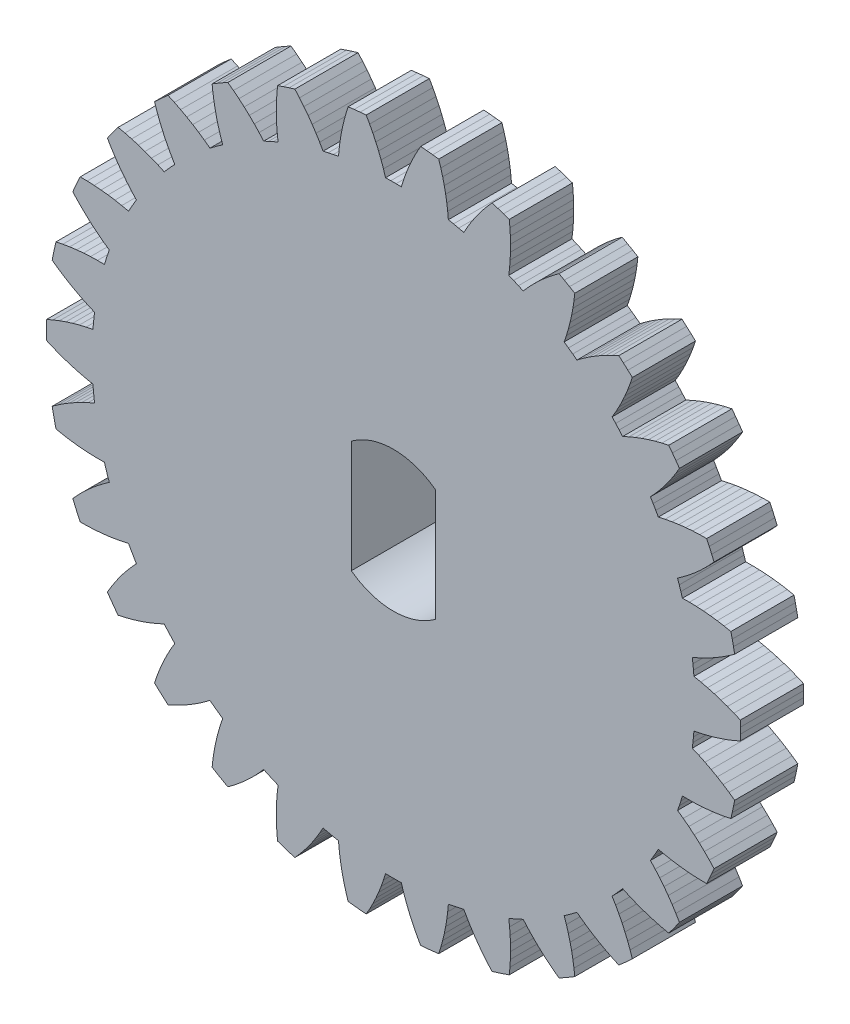
SolidWorks part; units mm, degrees
ref_plane "Front Plane" through (0, 0, 0) normal (0, 0, 1) x (1, 0, 0)
ref_plane "Top Plane" through (0, 0, 0) normal (0, 1, 0) x (1, 0, 0)
ref_plane "Right Plane" through (0, 0, 0) normal (1, 0, 0) x (0, 0, -1)
sketch "Sketch2" plane through (0, 0, 0) normal (0, 0, 1) x (1, 0, 0)
  line L20 (0.2811, 27.0228) -> (0.3553, 27.2598)
  line L21 (0.3553, 27.2598) -> (0.4378, 27.494)
  line L22 (0.4378, 27.494) -> (0.5284, 27.7252)
  line L23 (0.5284, 27.7252) -> (0.6271, 27.953)
  line L24 (0.6271, 27.953) -> (0.7337, 28.1773)
  line L25 (0.7337, 28.1773) -> (0.8481, 28.3976)
  line L26 (0.8481, 28.3976) -> (0.9702, 28.6139)
  line L27 (1.1852, 28.5951) -> (0.9702, 28.6139)
  line L28 (1.3998, 28.5725) -> (1.1852, 28.5951)
  line L29 (1.614, 28.5462) -> (1.3998, 28.5725)
  line L30 (1.614, 28.5462) -> (1.6885, 28.3093)
  line L31 (1.6885, 28.3093) -> (1.7546, 28.07)
  line L32 (1.7546, 28.07) -> (1.8122, 27.8285)
  line L33 (1.8122, 27.8285) -> (1.8614, 27.5851)
  line L34 (1.8614, 27.5851) -> (1.9019, 27.3401)
  line L35 (1.9019, 27.3401) -> (1.9339, 27.0939)
  line L36 (1.9339, 27.0939) -> (1.9572, 26.8467)
  line L37 (1.9572, 26.8467) -> (2.1412, 26.8109)
  line L38 (2.1412, 26.8109) -> (2.3246, 26.7719)
  line L39 (2.3246, 26.7719) -> (2.5072, 26.7298)
  line L41 (2.5072, 26.7298) -> (2.6291, 26.9461)
  line L42 (2.6291, 26.9461) -> (2.7584, 27.1581)
  line L43 (2.7584, 27.1581) -> (2.8951, 27.3653)
  line L44 (2.8951, 27.3653) -> (3.039, 27.5677)
  line L45 (3.039, 27.5677) -> (3.1899, 27.7649)
  line L46 (3.1899, 27.7649) -> (3.3476, 27.9567)
  line L47 (3.3476, 27.9567) -> (3.512, 28.1428)
  line L48 (3.7184, 28.0797) -> (3.512, 28.1428)
  line L49 (3.9236, 28.013) -> (3.7184, 28.0797)
  line L50 (4.1277, 27.9427) -> (3.9236, 28.013)
  line L51 (4.1277, 27.9427) -> (4.1513, 27.6955)
  line L52 (4.1513, 27.6955) -> (4.1661, 27.4477)
  line L53 (4.1661, 27.4477) -> (4.1723, 27.1995)
  line L54 (4.1723, 27.1995) -> (4.1698, 26.9512)
  line L55 (4.1698, 26.9512) -> (4.1586, 26.7031)
  line L56 (4.1586, 26.7031) -> (4.1386, 26.4556)
  line L57 (4.1386, 26.4556) -> (4.11, 26.209)
  line L58 (4.11, 26.209) -> (4.2826, 26.1357)
  line L59 (4.2826, 26.1357) -> (4.4538, 26.0595)
  line L60 (4.4538, 26.0595) -> (4.6237, 25.9803)
  line L61 (4.6237, 25.9803) -> (4.7879, 26.1666)
  line L62 (4.7879, 26.1666) -> (4.9585, 26.347)
  line L63 (4.9585, 26.347) -> (5.1353, 26.5213)
  line L64 (5.1353, 26.5213) -> (5.3181, 26.6893)
  line L65 (5.3181, 26.6893) -> (5.5067, 26.8508)
  line L66 (5.5067, 26.8508) -> (5.7008, 27.0056)
  line L67 (5.7008, 27.0056) -> (5.9003, 27.1535)
  line L68 (6.0891, 27.0489) -> (5.9003, 27.1535)
  line L69 (6.276, 26.941) -> (6.0891, 27.0489)
  line L70 (6.461, 26.8298) -> (6.276, 26.941)
  line L71 (6.461, 26.8298) -> (6.4326, 26.5831)
  line L72 (6.4326, 26.5831) -> (6.3956, 26.3376)
  line L73 (6.3956, 26.3376) -> (6.3501, 26.0935)
  line L74 (6.3501, 26.0935) -> (6.296, 25.8512)
  line L75 (6.296, 25.8512) -> (6.2334, 25.6109)
  line L76 (6.2334, 25.6109) -> (6.1625, 25.3729)
  line L77 (6.1625, 25.3729) -> (6.0832, 25.1376)
  line L78 (6.0832, 25.1376) -> (6.2368, 25.0301)
  line L79 (6.2368, 25.0301) -> (6.3884, 24.9199)
  line L80 (6.3884, 24.9199) -> (6.5381, 24.8071)
  line L81 (6.5381, 24.8071) -> (6.7374, 24.9552)
  line L82 (6.7374, 24.9552) -> (6.9418, 25.0962)
  line L83 (6.9418, 25.0962) -> (7.151, 25.23)
  line L84 (7.151, 25.23) -> (7.3648, 25.3563)
  line L85 (7.3648, 25.3563) -> (7.5828, 25.4751)
  line L86 (7.5828, 25.4751) -> (7.8049, 25.5861)
  line L87 (7.8049, 25.5861) -> (8.0307, 25.6893)
  line L88 (8.1936, 25.5477) -> (8.0307, 25.6893)
  line L89 (8.354, 25.4033) -> (8.1936, 25.5477)
  line L90 (8.5118, 25.2561) -> (8.354, 25.4033)
  line L91 (8.5118, 25.2561) -> (8.4328, 25.0207)
  line L92 (8.4328, 25.0207) -> (8.3456, 24.7882)
  line L93 (8.3456, 24.7882) -> (8.2503, 24.559)
  line L94 (8.2503, 24.559) -> (8.147, 24.3332)
  line L95 (8.147, 24.3332) -> (8.0359, 24.1111)
  line L96 (8.0359, 24.1111) -> (7.917, 23.8931)
  line L97 (7.917, 23.8931) -> (7.7905, 23.6794)
  line L98 (7.7905, 23.6794) -> (7.9184, 23.5424)
  line L99 (7.9184, 23.5424) -> (8.0438, 23.4031)
  line L100 (8.0438, 23.4031) -> (8.1668, 23.2616)
  line L101 (8.1668, 23.2616) -> (8.3925, 23.365)
  line L102 (8.3925, 23.365) -> (8.6217, 23.4604)
  line L103 (8.6217, 23.4604) -> (8.8542, 23.5478)
  line L104 (8.8542, 23.5478) -> (9.0895, 23.6269)
  line L105 (9.0895, 23.6269) -> (9.3275, 23.6977)
  line L106 (9.3275, 23.6977) -> (9.5678, 23.7602)
  line L107 (9.5678, 23.7602) -> (9.8102, 23.8141)
  line L108 (9.9401, 23.6418) -> (9.8102, 23.8141)
  line L109 (10.0669, 23.4672) -> (9.9401, 23.6418)
  line L110 (10.1907, 23.2904) -> (10.0669, 23.4672)
  line L111 (10.1907, 23.2904) -> (10.0645, 23.0766)
  line L112 (10.0645, 23.0766) -> (9.9309, 22.8673)
  line L113 (9.9309, 22.8673) -> (9.79, 22.6629)
  line L114 (9.79, 22.6629) -> (9.642, 22.4635)
  line L115 (9.642, 22.4635) -> (9.4871, 22.2694)
  line L116 (9.4871, 22.2694) -> (9.3255, 22.0809)
  line L117 (9.3255, 22.0809) -> (9.1574, 21.8981)
  line L118 (9.1574, 21.8981) -> (9.2539, 21.7375)
  line L119 (9.2539, 21.7375) -> (9.3476, 21.5751)
  line L120 (9.3476, 21.5751) -> (9.4385, 21.4112)
  line L121 (9.4385, 21.4112) -> (9.6808, 21.4654)
  line L122 (9.6808, 21.4654) -> (9.9249, 21.5111)
  line L123 (9.9249, 21.5111) -> (10.1704, 21.5482)
  line L124 (10.1704, 21.5482) -> (10.4171, 21.5767)
  line L125 (10.4171, 21.5767) -> (10.6646, 21.5965)
  line L126 (10.6646, 21.5965) -> (10.9126, 21.6076)
  line L127 (10.9126, 21.6076) -> (11.1609, 21.61)
  line L128 (11.2521, 21.4144) -> (11.1609, 21.61)
  line L129 (11.3399, 21.2172) -> (11.2521, 21.4144)
  line L130 (11.4242, 21.0186) -> (11.3399, 21.2172)
  line L131 (11.4242, 21.0186) -> (11.2563, 20.8357)
  line L132 (11.2563, 20.8357) -> (11.0821, 20.6588)
  line L133 (11.0821, 20.6588) -> (10.9017, 20.4881)
  line L134 (10.9017, 20.4881) -> (10.7155, 20.3238)
  line L135 (10.7155, 20.3238) -> (10.5237, 20.1662)
  line L136 (10.5237, 20.1662) -> (10.3264, 20.0154)
  line L137 (10.3264, 20.0154) -> (10.124, 19.8716)
  line L138 (10.124, 19.8716) -> (10.185, 19.6944)
  line L139 (10.185, 19.6944) -> (10.2429, 19.5161)
  line L140 (10.2429, 19.5161) -> (10.2977, 19.3368)
  line L141 (10.2977, 19.3368) -> (10.546, 19.3395)
  line L142 (10.546, 19.3395) -> (10.7943, 19.3334)
  line L143 (10.7943, 19.3334) -> (11.0421, 19.3187)
  line L144 (11.0421, 19.3187) -> (11.2893, 19.2952)
  line L145 (11.2893, 19.2952) -> (11.5355, 19.2631)
  line L146 (11.5355, 19.2631) -> (11.7805, 19.2224)
  line L147 (11.7805, 19.2224) -> (12.0238, 19.1732)
  line L148 (12.0724, 18.9629) -> (12.0238, 19.1732)
  line L149 (12.1172, 18.7518) -> (12.0724, 18.9629)
  line L150 (12.1584, 18.5399) -> (12.1172, 18.7518)
  line L151 (12.1584, 18.5399) -> (11.9561, 18.3959)
  line L152 (11.9561, 18.3959) -> (11.7489, 18.2591)
  line L153 (11.7489, 18.2591) -> (11.5371, 18.1297)
  line L154 (11.5371, 18.1297) -> (11.3208, 18.0077)
  line L155 (11.3208, 18.0077) -> (11.1003, 17.8934)
  line L156 (11.1003, 17.8934) -> (10.876, 17.7869)
  line L157 (10.876, 17.7869) -> (10.6481, 17.6884)
  line L158 (10.6481, 17.6884) -> (10.671, 17.5023)
  line L159 (10.671, 17.5023) -> (10.6906, 17.3159)
  line L160 (10.6906, 17.3159) -> (10.7069, 17.1291)
  line L161 (10.7069, 17.1291) -> (10.9503, 17.0801)
  line L162 (10.9503, 17.0801) -> (11.1919, 17.0226)
  line L163 (11.1919, 17.0226) -> (11.4312, 16.9566)
  line L164 (11.4312, 16.9566) -> (11.6682, 16.8823)
  line L165 (11.6682, 16.8823) -> (11.9023, 16.7997)
  line L166 (11.9023, 16.7997) -> (12.1335, 16.709)
  line L167 (12.1335, 16.709) -> (12.3613, 16.6102)
  line L168 (12.365, 16.3944) -> (12.3613, 16.6102)
  line L169 (12.365, 16.1786) -> (12.365, 16.3944)
  line L170 (12.3613, 15.9628) -> (12.365, 16.1786)
  line L171 (12.3613, 15.9628) -> (12.1335, 15.864)
  line L172 (12.1335, 15.864) -> (11.9023, 15.7733)
  line L173 (11.9023, 15.7733) -> (11.6682, 15.6907)
  line L174 (11.6682, 15.6907) -> (11.4312, 15.6164)
  line L175 (11.4312, 15.6164) -> (11.1919, 15.5504)
  line L176 (11.1919, 15.5504) -> (10.9503, 15.4929)
  line L177 (10.9503, 15.4929) -> (10.7069, 15.4438)
  line L178 (10.7069, 15.4438) -> (10.6906, 15.2571)
  line L179 (10.6906, 15.2571) -> (10.671, 15.0707)
  line L180 (10.671, 15.0707) -> (10.6481, 14.8846)
  line L181 (10.6481, 14.8846) -> (10.876, 14.7861)
  line L182 (10.876, 14.7861) -> (11.1003, 14.6796)
  line L183 (11.1003, 14.6796) -> (11.3208, 14.5653)
  line L184 (11.3208, 14.5653) -> (11.5371, 14.4433)
  line L185 (11.5371, 14.4433) -> (11.7489, 14.3139)
  line L186 (11.7489, 14.3139) -> (11.9561, 14.1771)
  line L187 (11.9561, 14.1771) -> (12.1584, 14.0331)
  line L188 (12.1172, 13.8212) -> (12.1584, 14.0331)
  line L189 (12.0724, 13.6101) -> (12.1172, 13.8212)
  line L190 (12.0238, 13.3998) -> (12.0724, 13.6101)
  line L191 (12.0238, 13.3998) -> (11.7805, 13.3506)
  line L192 (11.7805, 13.3506) -> (11.5355, 13.3098)
  line L193 (11.5355, 13.3098) -> (11.2893, 13.2778)
  line L194 (11.2893, 13.2778) -> (11.0421, 13.2543)
  line L195 (11.0421, 13.2543) -> (10.7943, 13.2396)
  line L196 (10.7943, 13.2396) -> (10.546, 13.2335)
  line L197 (10.546, 13.2335) -> (10.2977, 13.2362)
  line L198 (10.2977, 13.2362) -> (10.2429, 13.0569)
  line L199 (10.2429, 13.0569) -> (10.185, 12.8786)
  line L200 (10.185, 12.8786) -> (10.124, 12.7014)
  line L201 (10.124, 12.7014) -> (10.3264, 12.5576)
  line L202 (10.3264, 12.5576) -> (10.5237, 12.4068)
  line L203 (10.5237, 12.4068) -> (10.7155, 12.2492)
  line L204 (10.7155, 12.2492) -> (10.9017, 12.0849)
  line L205 (10.9017, 12.0849) -> (11.0821, 11.9142)
  line L206 (11.0821, 11.9142) -> (11.2563, 11.7373)
  line L207 (11.2563, 11.7373) -> (11.4242, 11.5544)
  line L208 (11.3399, 11.3558) -> (11.4242, 11.5544)
  line L209 (11.2521, 11.1586) -> (11.3399, 11.3558)
  line L210 (11.1609, 10.963) -> (11.2521, 11.1586)
  line L211 (11.1609, 10.963) -> (10.9126, 10.9654)
  line L212 (10.9126, 10.9654) -> (10.6646, 10.9765)
  line L213 (10.6646, 10.9765) -> (10.4171, 10.9963)
  line L214 (10.4171, 10.9963) -> (10.1704, 11.0248)
  line L215 (10.1704, 11.0248) -> (9.9249, 11.0619)
  line L216 (9.9249, 11.0619) -> (9.6808, 11.1076)
  line L217 (9.6808, 11.1076) -> (9.4385, 11.1618)
  line L218 (9.4385, 11.1618) -> (9.3476, 10.9979)
  line L219 (9.3476, 10.9979) -> (9.2539, 10.8355)
  line L220 (9.2539, 10.8355) -> (9.1574, 10.6748)
  line L221 (9.1574, 10.6748) -> (9.3255, 10.4921)
  line L222 (9.3255, 10.4921) -> (9.4871, 10.3036)
  line L223 (9.4871, 10.3036) -> (9.642, 10.1095)
  line L224 (9.642, 10.1095) -> (9.79, 9.9101)
  line L225 (9.79, 9.9101) -> (9.9309, 9.7057)
  line L226 (9.9309, 9.7057) -> (10.0645, 9.4964)
  line L227 (10.0645, 9.4964) -> (10.1907, 9.2826)
  line L228 (10.0669, 9.1058) -> (10.1907, 9.2826)
  line L229 (9.9401, 8.9312) -> (10.0669, 9.1058)
  line L230 (9.8102, 8.7589) -> (9.9401, 8.9312)
  line L231 (9.8102, 8.7589) -> (9.5678, 8.8128)
  line L232 (9.5678, 8.8128) -> (9.3275, 8.8753)
  line L233 (9.3275, 8.8753) -> (9.0895, 8.9461)
  line L234 (9.0895, 8.9461) -> (8.8542, 9.0252)
  line L235 (8.8542, 9.0252) -> (8.6217, 9.1126)
  line L236 (8.6217, 9.1126) -> (8.3925, 9.208)
  line L237 (8.3925, 9.208) -> (8.1668, 9.3114)
  line L238 (8.1668, 9.3114) -> (8.0438, 9.1699)
  line L239 (8.0438, 9.1699) -> (7.9184, 9.0306)
  line L240 (7.9184, 9.0306) -> (7.7905, 8.8936)
  line L241 (7.7905, 8.8936) -> (7.917, 8.6799)
  line L242 (7.917, 8.6799) -> (8.0359, 8.4619)
  line L243 (8.0359, 8.4619) -> (8.147, 8.2398)
  line L244 (8.147, 8.2398) -> (8.2503, 8.014)
  line L245 (8.2503, 8.014) -> (8.3456, 7.7848)
  line L246 (8.3456, 7.7848) -> (8.4328, 7.5523)
  line L247 (8.4328, 7.5523) -> (8.5118, 7.3169)
  line L248 (8.354, 7.1697) -> (8.5118, 7.3169)
  line L249 (8.1936, 7.0253) -> (8.354, 7.1697)
  line L250 (8.0307, 6.8837) -> (8.1936, 7.0253)
  line L251 (8.0307, 6.8837) -> (7.8049, 6.9869)
  line L252 (7.8049, 6.9869) -> (7.5828, 7.0979)
  line L253 (7.5828, 7.0979) -> (7.3647, 7.2167)
  line L254 (7.3647, 7.2167) -> (7.151, 7.343)
  line L255 (7.151, 7.343) -> (6.9418, 7.4768)
  line L256 (6.9418, 7.4768) -> (6.7374, 7.6178)
  line L257 (6.7374, 7.6178) -> (6.5381, 7.7659)
  line L258 (6.5381, 7.7659) -> (6.3884, 7.6531)
  line L259 (6.3884, 7.6531) -> (6.2368, 7.5429)
  line L260 (6.2368, 7.5429) -> (6.0832, 7.4354)
  line L261 (6.0832, 7.4354) -> (6.1625, 7.2)
  line L262 (6.1625, 7.2) -> (6.2334, 6.9621)
  line L263 (6.2334, 6.9621) -> (6.296, 6.7218)
  line L264 (6.296, 6.7218) -> (6.3501, 6.4795)
  line L265 (6.3501, 6.4795) -> (6.3956, 6.2354)
  line L266 (6.3956, 6.2354) -> (6.4326, 5.9899)
  line L267 (6.4326, 5.9899) -> (6.4609, 5.7432)
  line L268 (6.276, 5.632) -> (6.4609, 5.7432)
  line L269 (6.0891, 5.5241) -> (6.276, 5.632)
  line L270 (5.9003, 5.4195) -> (6.0891, 5.5241)
  line L271 (5.9003, 5.4195) -> (5.7008, 5.5674)
  line L272 (5.7008, 5.5674) -> (5.5067, 5.7222)
  line L273 (5.5067, 5.7222) -> (5.3181, 5.8837)
  line L274 (5.3181, 5.8837) -> (5.1353, 6.0517)
  line L275 (5.1353, 6.0517) -> (4.9585, 6.226)
  line L276 (4.9585, 6.226) -> (4.7879, 6.4064)
  line L277 (4.7879, 6.4064) -> (4.6237, 6.5927)
  line L278 (4.6237, 6.5927) -> (4.4538, 6.5135)
  line L279 (4.4538, 6.5135) -> (4.2826, 6.4372)
  line L280 (4.2826, 6.4372) -> (4.11, 6.364)
  line L281 (4.11, 6.364) -> (4.1386, 6.1174)
  line L282 (4.1386, 6.1174) -> (4.1585, 5.8699)
  line L283 (4.1585, 5.8699) -> (4.1698, 5.6218)
  line L284 (4.1698, 5.6218) -> (4.1723, 5.3735)
  line L285 (4.1723, 5.3735) -> (4.1661, 5.1253)
  line L286 (4.1661, 5.1253) -> (4.1512, 4.8775)
  line L287 (4.1512, 4.8775) -> (4.1277, 4.6303)
  line L288 (3.9236, 4.56) -> (4.1277, 4.6303)
  line L289 (3.7184, 4.4933) -> (3.9236, 4.56)
  line L290 (3.512, 4.4302) -> (3.7184, 4.4933)
  line L291 (3.512, 4.4302) -> (3.3476, 4.6163)
  line L292 (3.3476, 4.6163) -> (3.1899, 4.8081)
  line L293 (3.1899, 4.8081) -> (3.039, 5.0053)
  line L294 (3.039, 5.0053) -> (2.8951, 5.2076)
  line L295 (2.8951, 5.2076) -> (2.7584, 5.4149)
  line L296 (2.7584, 5.4149) -> (2.629, 5.6269)
  line L297 (2.629, 5.6269) -> (2.5072, 5.8432)
  line L298 (2.5072, 5.8432) -> (2.3246, 5.8011)
  line L299 (2.3246, 5.8011) -> (2.1412, 5.7621)
  line L300 (2.1412, 5.7621) -> (1.9572, 5.7263)
  line L301 (1.9572, 5.7263) -> (1.9339, 5.4791)
  line L302 (1.9339, 5.4791) -> (1.9019, 5.2329)
  line L303 (1.9019, 5.2329) -> (1.8613, 4.9879)
  line L304 (1.8613, 4.9879) -> (1.8122, 4.7445)
  line L305 (1.8122, 4.7445) -> (1.7545, 4.503)
  line L306 (1.7545, 4.503) -> (1.6885, 4.2637)
  line L307 (1.6885, 4.2637) -> (1.614, 4.0268)
  line L308 (1.3998, 4.0005) -> (1.614, 4.0268)
  line L309 (1.1852, 3.9779) -> (1.3998, 4.0005)
  line L310 (0.9702, 3.9591) -> (1.1852, 3.9779)
  line L311 (0.9702, 3.9591) -> (0.8481, 4.1754)
  line L312 (0.8481, 4.1754) -> (0.7337, 4.3957)
  line L313 (0.7337, 4.3957) -> (0.6271, 4.62)
  line L314 (0.6271, 4.62) -> (0.5284, 4.8478)
  line L315 (0.5284, 4.8478) -> (0.4378, 5.079)
  line L316 (0.4378, 5.079) -> (0.3553, 5.3132)
  line L317 (0.3553, 5.3132) -> (0.2811, 5.5502)
  line L318 (0.2811, 5.5502) -> (0.0937, 5.5469)
  line L319 (0.0937, 5.5469) -> (-0.0937, 5.5469)
  line L320 (-0.0937, 5.5469) -> (-0.2811, 5.5502)
  line L321 (-0.2811, 5.5502) -> (-0.3553, 5.3132)
  line L322 (-0.3553, 5.3132) -> (-0.4378, 5.079)
  line L323 (-0.4378, 5.079) -> (-0.5284, 4.8478)
  line L324 (-0.5284, 4.8478) -> (-0.6271, 4.62)
  line L325 (-0.6271, 4.62) -> (-0.7337, 4.3957)
  line L326 (-0.7337, 4.3957) -> (-0.8481, 4.1754)
  line L327 (-0.8481, 4.1754) -> (-0.9702, 3.9591)
  line L328 (-1.1852, 3.9779) -> (-0.9702, 3.9591)
  line L329 (-1.3998, 4.0005) -> (-1.1852, 3.9779)
  line L330 (-1.614, 4.0268) -> (-1.3998, 4.0005)
  line L331 (-1.614, 4.0268) -> (-1.6885, 4.2637)
  line L332 (-1.6885, 4.2637) -> (-1.7546, 4.503)
  line L333 (-1.7546, 4.503) -> (-1.8122, 4.7445)
  line L334 (-1.8122, 4.7445) -> (-1.8614, 4.9879)
  line L335 (-1.8614, 4.9879) -> (-1.9019, 5.2329)
  line L336 (-1.9019, 5.2329) -> (-1.9339, 5.4791)
  line L337 (-1.9339, 5.4791) -> (-1.9572, 5.7263)
  line L338 (-1.9572, 5.7263) -> (-2.1412, 5.7621)
  line L339 (-2.1412, 5.7621) -> (-2.3246, 5.8011)
  line L340 (-2.3246, 5.8011) -> (-2.5072, 5.8432)
  line L341 (-2.5072, 5.8432) -> (-2.6291, 5.6269)
  line L342 (-2.6291, 5.6269) -> (-2.7584, 5.4149)
  line L343 (-2.7584, 5.4149) -> (-2.8951, 5.2077)
  line L344 (-2.8951, 5.2077) -> (-3.039, 5.0053)
  line L345 (-3.039, 5.0053) -> (-3.1899, 4.8081)
  line L346 (-3.1899, 4.8081) -> (-3.3476, 4.6163)
  line L347 (-3.3476, 4.6163) -> (-3.512, 4.4302)
  line L348 (-3.7184, 4.4933) -> (-3.512, 4.4302)
  line L349 (-3.9236, 4.56) -> (-3.7184, 4.4933)
  line L350 (-4.1277, 4.6303) -> (-3.9236, 4.56)
  line L351 (-4.1277, 4.6303) -> (-4.1513, 4.8775)
  line L352 (-4.1513, 4.8775) -> (-4.1661, 5.1253)
  line L353 (-4.1661, 5.1253) -> (-4.1723, 5.3735)
  line L354 (-4.1723, 5.3735) -> (-4.1698, 5.6218)
  line L355 (-4.1698, 5.6218) -> (-4.1586, 5.8699)
  line L356 (-4.1586, 5.8699) -> (-4.1386, 6.1174)
  line L357 (-4.1386, 6.1174) -> (-4.11, 6.364)
  line L358 (-4.11, 6.364) -> (-4.2826, 6.4372)
  line L359 (-4.2826, 6.4372) -> (-4.4538, 6.5135)
  line L360 (-4.4538, 6.5135) -> (-4.6237, 6.5927)
  line L361 (-4.6237, 6.5927) -> (-4.7879, 6.4064)
  line L362 (-4.7879, 6.4064) -> (-4.9585, 6.226)
  line L363 (-4.9585, 6.226) -> (-5.1353, 6.0517)
  line L364 (-5.1353, 6.0517) -> (-5.3181, 5.8837)
  line L365 (-5.3181, 5.8837) -> (-5.5067, 5.7222)
  line L366 (-5.5067, 5.7222) -> (-5.7008, 5.5674)
  line L367 (-5.7008, 5.5674) -> (-5.9003, 5.4195)
  line L368 (-6.0891, 5.5241) -> (-5.9003, 5.4195)
  line L369 (-6.276, 5.632) -> (-6.0891, 5.5241)
  line L370 (-6.461, 5.7432) -> (-6.276, 5.632)
  line L371 (-6.461, 5.7432) -> (-6.4326, 5.9899)
  line L372 (-6.4326, 5.9899) -> (-6.3956, 6.2354)
  line L373 (-6.3956, 6.2354) -> (-6.3501, 6.4795)
  line L374 (-6.3501, 6.4795) -> (-6.296, 6.7218)
  line L375 (-6.296, 6.7218) -> (-6.2334, 6.9621)
  line L376 (-6.2334, 6.9621) -> (-6.1625, 7.2)
  line L377 (-6.1625, 7.2) -> (-6.0832, 7.4354)
  line L378 (-6.0832, 7.4354) -> (-6.2368, 7.5429)
  line L379 (-6.2368, 7.5429) -> (-6.3884, 7.6531)
  line L380 (-6.3884, 7.6531) -> (-6.5381, 7.7659)
  line L381 (-6.5381, 7.7659) -> (-6.7374, 7.6178)
  line L382 (-6.7374, 7.6178) -> (-6.9418, 7.4768)
  line L383 (-6.9418, 7.4768) -> (-7.151, 7.343)
  line L384 (-7.151, 7.343) -> (-7.3648, 7.2167)
  line L385 (-7.3648, 7.2167) -> (-7.5828, 7.0979)
  line L386 (-7.5828, 7.0979) -> (-7.8049, 6.9869)
  line L387 (-7.8049, 6.9869) -> (-8.0307, 6.8837)
  line L388 (-8.1936, 7.0253) -> (-8.0307, 6.8837)
  line L389 (-8.354, 7.1697) -> (-8.1936, 7.0253)
  line L390 (-8.5118, 7.3169) -> (-8.354, 7.1697)
  line L391 (-8.5118, 7.3169) -> (-8.4328, 7.5523)
  line L392 (-8.4328, 7.5523) -> (-8.3456, 7.7848)
  line L393 (-8.3456, 7.7848) -> (-8.2503, 8.014)
  line L394 (-8.2503, 8.014) -> (-8.147, 8.2398)
  line L395 (-8.147, 8.2398) -> (-8.0359, 8.4619)
  line L396 (-8.0359, 8.4619) -> (-7.917, 8.6799)
  line L397 (-7.917, 8.6799) -> (-7.7905, 8.8936)
  line L398 (-7.7905, 8.8936) -> (-7.9184, 9.0306)
  line L399 (-7.9184, 9.0306) -> (-8.0438, 9.1699)
  line L400 (-8.0438, 9.1699) -> (-8.1668, 9.3114)
  line L401 (-8.1668, 9.3114) -> (-8.3925, 9.208)
  line L402 (-8.3925, 9.208) -> (-8.6218, 9.1126)
  line L403 (-8.6218, 9.1126) -> (-8.8542, 9.0252)
  line L404 (-8.8542, 9.0252) -> (-9.0895, 8.9461)
  line L405 (-9.0895, 8.9461) -> (-9.3275, 8.8753)
  line L406 (-9.3275, 8.8753) -> (-9.5678, 8.8128)
  line L407 (-9.5678, 8.8128) -> (-9.8102, 8.7589)
  line L408 (-9.9401, 8.9312) -> (-9.8102, 8.7589)
  line L409 (-10.0669, 9.1058) -> (-9.9401, 8.9312)
  line L410 (-10.1907, 9.2826) -> (-10.0669, 9.1058)
  line L411 (-10.1907, 9.2826) -> (-10.0645, 9.4964)
  line L412 (-10.0645, 9.4964) -> (-9.9309, 9.7057)
  line L413 (-9.9309, 9.7057) -> (-9.79, 9.9101)
  line L414 (-9.79, 9.9101) -> (-9.642, 10.1095)
  line L415 (-9.642, 10.1095) -> (-9.4871, 10.3036)
  line L416 (-9.4871, 10.3036) -> (-9.3255, 10.4921)
  line L417 (-9.3255, 10.4921) -> (-9.1574, 10.6749)
  line L418 (-9.1574, 10.6749) -> (-9.2539, 10.8355)
  line L419 (-9.2539, 10.8355) -> (-9.3476, 10.9979)
  line L420 (-9.3476, 10.9979) -> (-9.4385, 11.1618)
  line L421 (-9.4385, 11.1618) -> (-9.6808, 11.1076)
  line L422 (-9.6808, 11.1076) -> (-9.9249, 11.0619)
  line L423 (-9.9249, 11.0619) -> (-10.1704, 11.0248)
  line L424 (-10.1704, 11.0248) -> (-10.4171, 10.9963)
  line L425 (-10.4171, 10.9963) -> (-10.6646, 10.9765)
  line L426 (-10.6646, 10.9765) -> (-10.9126, 10.9654)
  line L427 (-10.9126, 10.9654) -> (-11.1609, 10.963)
  line L428 (-11.2521, 11.1586) -> (-11.1609, 10.963)
  line L429 (-11.3399, 11.3558) -> (-11.2521, 11.1586)
  line L430 (-11.4242, 11.5544) -> (-11.3399, 11.3558)
  line L431 (-11.4242, 11.5544) -> (-11.2563, 11.7373)
  line L432 (-11.2563, 11.7373) -> (-11.0821, 11.9142)
  line L433 (-11.0821, 11.9142) -> (-10.9017, 12.0849)
  line L434 (-10.9017, 12.0849) -> (-10.7155, 12.2492)
  line L435 (-10.7155, 12.2492) -> (-10.5237, 12.4068)
  line L436 (-10.5237, 12.4068) -> (-10.3264, 12.5576)
  line L437 (-10.3264, 12.5576) -> (-10.124, 12.7014)
  line L438 (-10.124, 12.7014) -> (-10.185, 12.8786)
  line L439 (-10.185, 12.8786) -> (-10.243, 13.0569)
  line L440 (-10.243, 13.0569) -> (-10.2978, 13.2362)
  line L441 (-10.2978, 13.2362) -> (-10.546, 13.2335)
  line L442 (-10.546, 13.2335) -> (-10.7943, 13.2396)
  line L443 (-10.7943, 13.2396) -> (-11.0421, 13.2543)
  line L444 (-11.0421, 13.2543) -> (-11.2893, 13.2778)
  line L445 (-11.2893, 13.2778) -> (-11.5355, 13.3099)
  line L446 (-11.5355, 13.3099) -> (-11.7805, 13.3506)
  line L447 (-11.7805, 13.3506) -> (-12.0238, 13.3998)
  line L448 (-12.0724, 13.6101) -> (-12.0238, 13.3998)
  line L449 (-12.1173, 13.8212) -> (-12.0724, 13.6101)
  line L450 (-12.1584, 14.0331) -> (-12.1173, 13.8212)
  line L451 (-12.1584, 14.0331) -> (-11.9562, 14.1771)
  line L452 (-11.9562, 14.1771) -> (-11.7489, 14.3139)
  line L453 (-11.7489, 14.3139) -> (-11.5371, 14.4433)
  line L454 (-11.5371, 14.4433) -> (-11.3208, 14.5653)
  line L455 (-11.3208, 14.5653) -> (-11.1004, 14.6796)
  line L456 (-11.1004, 14.6796) -> (-10.876, 14.7861)
  line L457 (-10.876, 14.7861) -> (-10.6481, 14.8846)
  line L458 (-10.6481, 14.8846) -> (-10.671, 15.0707)
  line L459 (-10.671, 15.0707) -> (-10.6906, 15.2571)
  line L460 (-10.6906, 15.2571) -> (-10.7069, 15.4438)
  line L461 (-10.7069, 15.4438) -> (-10.9503, 15.4929)
  line L462 (-10.9503, 15.4929) -> (-11.1919, 15.5504)
  line L463 (-11.1919, 15.5504) -> (-11.4313, 15.6164)
  line L464 (-11.4313, 15.6164) -> (-11.6682, 15.6907)
  line L465 (-11.6682, 15.6907) -> (-11.9023, 15.7733)
  line L466 (-11.9023, 15.7733) -> (-12.1335, 15.864)
  line L467 (-12.1335, 15.864) -> (-12.3613, 15.9628)
  line L468 (-12.365, 16.1786) -> (-12.3613, 15.9628)
  line L469 (-12.365, 16.3944) -> (-12.365, 16.1786)
  line L470 (-12.3613, 16.6102) -> (-12.365, 16.3944)
  line L471 (-12.3613, 16.6102) -> (-12.1335, 16.709)
  line L472 (-12.1335, 16.709) -> (-11.9023, 16.7997)
  line L473 (-11.9023, 16.7997) -> (-11.6682, 16.8823)
  line L474 (-11.6682, 16.8823) -> (-11.4313, 16.9566)
  line L475 (-11.4313, 16.9566) -> (-11.1919, 17.0226)
  line L476 (-11.1919, 17.0226) -> (-10.9503, 17.0801)
  line L477 (-10.9503, 17.0801) -> (-10.7069, 17.1292)
  line L478 (-10.7069, 17.1292) -> (-10.6906, 17.3159)
  line L479 (-10.6906, 17.3159) -> (-10.671, 17.5023)
  line L480 (-10.671, 17.5023) -> (-10.6481, 17.6884)
  line L481 (-10.6481, 17.6884) -> (-10.876, 17.7869)
  line L482 (-10.876, 17.7869) -> (-11.1004, 17.8934)
  line L483 (-11.1004, 17.8934) -> (-11.3208, 18.0077)
  line L484 (-11.3208, 18.0077) -> (-11.5371, 18.1297)
  line L485 (-11.5371, 18.1297) -> (-11.7489, 18.2591)
  line L486 (-11.7489, 18.2591) -> (-11.9561, 18.3959)
  line L487 (-11.9561, 18.3959) -> (-12.1584, 18.5399)
  line L488 (-12.1173, 18.7518) -> (-12.1584, 18.5399)
  line L489 (-12.0724, 18.9629) -> (-12.1173, 18.7518)
  line L490 (-12.0238, 19.1732) -> (-12.0724, 18.9629)
  line L491 (-12.0238, 19.1732) -> (-11.7805, 19.2224)
  line L492 (-11.7805, 19.2224) -> (-11.5355, 19.2632)
  line L493 (-11.5355, 19.2632) -> (-11.2893, 19.2952)
  line L494 (-11.2893, 19.2952) -> (-11.0421, 19.3187)
  line L495 (-11.0421, 19.3187) -> (-10.7943, 19.3334)
  line L496 (-10.7943, 19.3334) -> (-10.546, 19.3395)
  line L497 (-10.546, 19.3395) -> (-10.2978, 19.3368)
  line L498 (-10.2978, 19.3368) -> (-10.2429, 19.5161)
  line L499 (-10.2429, 19.5161) -> (-10.185, 19.6944)
  line L500 (-10.185, 19.6944) -> (-10.124, 19.8716)
  line L501 (-10.124, 19.8716) -> (-10.3264, 20.0154)
  line L502 (-10.3264, 20.0154) -> (-10.5237, 20.1662)
  line L503 (-10.5237, 20.1662) -> (-10.7155, 20.3238)
  line L504 (-10.7155, 20.3238) -> (-10.9017, 20.4881)
  line L505 (-10.9017, 20.4881) -> (-11.0821, 20.6588)
  line L506 (-11.0821, 20.6588) -> (-11.2563, 20.8357)
  line L507 (-11.2563, 20.8357) -> (-11.4242, 21.0186)
  line L508 (-11.3399, 21.2172) -> (-11.4242, 21.0186)
  line L509 (-11.2521, 21.4144) -> (-11.3399, 21.2172)
  line L510 (-11.1609, 21.61) -> (-11.2521, 21.4144)
  line L511 (-11.1609, 21.61) -> (-10.9126, 21.6076)
  line L512 (-10.9126, 21.6076) -> (-10.6646, 21.5965)
  line L513 (-10.6646, 21.5965) -> (-10.4171, 21.5767)
  line L514 (-10.4171, 21.5767) -> (-10.1704, 21.5482)
  line L515 (-10.1704, 21.5482) -> (-9.9249, 21.5111)
  line L516 (-9.9249, 21.5111) -> (-9.6808, 21.4654)
  line L517 (-9.6808, 21.4654) -> (-9.4385, 21.4112)
  line L518 (-9.4385, 21.4112) -> (-9.3476, 21.5751)
  line L519 (-9.3476, 21.5751) -> (-9.2539, 21.7375)
  line L520 (-9.2539, 21.7375) -> (-9.1574, 21.8981)
  line L521 (-9.1574, 21.8981) -> (-9.3255, 22.0809)
  line L522 (-9.3255, 22.0809) -> (-9.4871, 22.2694)
  line L523 (-9.4871, 22.2694) -> (-9.642, 22.4635)
  line L524 (-9.642, 22.4635) -> (-9.79, 22.6629)
  line L525 (-9.79, 22.6629) -> (-9.9309, 22.8673)
  line L526 (-9.9309, 22.8673) -> (-10.0645, 23.0766)
  line L527 (-10.0645, 23.0766) -> (-10.1907, 23.2904)
  line L528 (-10.0669, 23.4672) -> (-10.1907, 23.2904)
  line L529 (-9.9401, 23.6418) -> (-10.0669, 23.4672)
  line L530 (-9.8102, 23.8141) -> (-9.9401, 23.6418)
  line L531 (-9.8102, 23.8141) -> (-9.5678, 23.7602)
  line L532 (-9.5678, 23.7602) -> (-9.3275, 23.6977)
  line L533 (-9.3275, 23.6977) -> (-9.0895, 23.6269)
  line L534 (-9.0895, 23.6269) -> (-8.8542, 23.5478)
  line L535 (-8.8542, 23.5478) -> (-8.6217, 23.4604)
  line L536 (-8.6217, 23.4604) -> (-8.3925, 23.365)
  line L537 (-8.3925, 23.365) -> (-8.1668, 23.2616)
  line L538 (-8.1668, 23.2616) -> (-8.0438, 23.4031)
  line L539 (-8.0438, 23.4031) -> (-7.9184, 23.5424)
  line L540 (-7.9184, 23.5424) -> (-7.7905, 23.6794)
  line L541 (-7.7905, 23.6794) -> (-7.917, 23.8931)
  line L542 (-7.917, 23.8931) -> (-8.0359, 24.1111)
  line L543 (-8.0359, 24.1111) -> (-8.147, 24.3332)
  line L544 (-8.147, 24.3332) -> (-8.2503, 24.559)
  line L545 (-8.2503, 24.559) -> (-8.3456, 24.7882)
  line L546 (-8.3456, 24.7882) -> (-8.4328, 25.0207)
  line L547 (-8.4328, 25.0207) -> (-8.5118, 25.2561)
  line L548 (-8.354, 25.4033) -> (-8.5118, 25.2561)
  line L549 (-8.1936, 25.5477) -> (-8.354, 25.4033)
  line L550 (-8.0307, 25.6893) -> (-8.1936, 25.5477)
  line L551 (-8.0307, 25.6893) -> (-7.8049, 25.5861)
  line L552 (-7.8049, 25.5861) -> (-7.5828, 25.4751)
  line L553 (-7.5828, 25.4751) -> (-7.3648, 25.3563)
  line L554 (-7.3648, 25.3563) -> (-7.151, 25.23)
  line L555 (-7.151, 25.23) -> (-6.9418, 25.0962)
  line L556 (-6.9418, 25.0962) -> (-6.7374, 24.9552)
  line L557 (-6.7374, 24.9552) -> (-6.5381, 24.8071)
  line L558 (-6.5381, 24.8071) -> (-6.3884, 24.9199)
  line L559 (-6.3884, 24.9199) -> (-6.2368, 25.0301)
  line L560 (-6.2368, 25.0301) -> (-6.0832, 25.1376)
  line L561 (-6.0832, 25.1376) -> (-6.1625, 25.373)
  line L562 (-6.1625, 25.373) -> (-6.2334, 25.6109)
  line L563 (-6.2334, 25.6109) -> (-6.296, 25.8512)
  line L564 (-6.296, 25.8512) -> (-6.3501, 26.0935)
  line L565 (-6.3501, 26.0935) -> (-6.3956, 26.3376)
  line L566 (-6.3956, 26.3376) -> (-6.4326, 26.5831)
  line L567 (-6.4326, 26.5831) -> (-6.461, 26.8298)
  line L568 (-6.276, 26.941) -> (-6.461, 26.8298)
  line L569 (-6.0891, 27.0489) -> (-6.276, 26.941)
  line L570 (-5.9003, 27.1535) -> (-6.0891, 27.0489)
  line L571 (-5.9003, 27.1535) -> (-5.7008, 27.0056)
  line L572 (-5.7008, 27.0056) -> (-5.5067, 26.8508)
  line L573 (-5.5067, 26.8508) -> (-5.3181, 26.6893)
  line L574 (-5.3181, 26.6893) -> (-5.1353, 26.5213)
  line L575 (-5.1353, 26.5213) -> (-4.9585, 26.347)
  line L576 (-4.9585, 26.347) -> (-4.7879, 26.1666)
  line L577 (-4.7879, 26.1666) -> (-4.6237, 25.9803)
  line L578 (-4.6237, 25.9803) -> (-4.4538, 26.0595)
  line L579 (-4.4538, 26.0595) -> (-4.2826, 26.1358)
  line L580 (-4.2826, 26.1358) -> (-4.11, 26.209)
  line L581 (-4.11, 26.209) -> (-4.1386, 26.4556)
  line L582 (-4.1386, 26.4556) -> (-4.1586, 26.7031)
  line L583 (-4.1586, 26.7031) -> (-4.1698, 26.9512)
  line L584 (-4.1698, 26.9512) -> (-4.1723, 27.1995)
  line L585 (-4.1723, 27.1995) -> (-4.1661, 27.4477)
  line L586 (-4.1661, 27.4477) -> (-4.1513, 27.6955)
  line L587 (-4.1513, 27.6955) -> (-4.1277, 27.9427)
  line L588 (-3.9236, 28.013) -> (-4.1277, 27.9427)
  line L589 (-3.7184, 28.0797) -> (-3.9236, 28.013)
  line L590 (-3.512, 28.1428) -> (-3.7184, 28.0797)
  line L591 (-3.512, 28.1428) -> (-3.3476, 27.9567)
  line L592 (-3.3476, 27.9567) -> (-3.1899, 27.7649)
  line L593 (-3.1899, 27.7649) -> (-3.039, 27.5677)
  line L594 (-3.039, 27.5677) -> (-2.8951, 27.3653)
  line L595 (-2.8951, 27.3653) -> (-2.7584, 27.1581)
  line L596 (-2.7584, 27.1581) -> (-2.6291, 26.9461)
  line L597 (-2.6291, 26.9461) -> (-2.5072, 26.7298)
  line L598 (-2.5072, 26.7298) -> (-2.3246, 26.7719)
  line L599 (-2.3246, 26.7719) -> (-2.1412, 26.8109)
  line L600 (-2.1412, 26.8109) -> (-1.9572, 26.8467)
  line L601 (-1.9572, 26.8467) -> (-1.9339, 27.0939)
  line L602 (-1.9339, 27.0939) -> (-1.9019, 27.3401)
  line L603 (-1.9019, 27.3401) -> (-1.8614, 27.5851)
  line L604 (-1.8614, 27.5851) -> (-1.8122, 27.8285)
  line L605 (-1.8122, 27.8285) -> (-1.7546, 28.07)
  line L606 (-1.7546, 28.07) -> (-1.6885, 28.3093)
  line L607 (-1.6885, 28.3093) -> (-1.614, 28.5462)
  line L608 (-1.3998, 28.5725) -> (-1.614, 28.5462)
  line L609 (-1.1852, 28.5951) -> (-1.3998, 28.5725)
  line L610 (-0.9702, 28.6139) -> (-1.1852, 28.5951)
  line L611 (-0.9702, 28.6139) -> (-0.8481, 28.3976)
  line L612 (-0.8481, 28.3976) -> (-0.7337, 28.1773)
  line L613 (-0.7337, 28.1773) -> (-0.6271, 27.953)
  line L614 (-0.6271, 27.953) -> (-0.5284, 27.7252)
  line L615 (-0.5284, 27.7252) -> (-0.4378, 27.494)
  line L616 (-0.4378, 27.494) -> (-0.3553, 27.2598)
  line L617 (-0.3553, 27.2598) -> (-0.2811, 27.0228)
  line L618 (-0.2811, 27.0228) -> (-0.0937, 27.0261)
  line L619 (-0.0937, 27.0261) -> (0.0937, 27.0261)
  line L620 (0.0937, 27.0261) -> (0.2811, 27.0228)
  circle A0 centre (0, 16.2865) radius 10.74 construction
  point P638 (0, 16.2865)
  dimension "D1" = 30
extrude "Boss-Extrude1" add sketch "Sketch2" along normal blind 2.25
sketch "Sketch3" plane through (0, 0, 2.25) normal (0, 0, 1) x (1, 0, 0)
  line L0 (-1.5, 18.2865) -> (-1.5, 14.2865)
  line L1 (-1.5, 16.2865) -> (1.5, 16.2865) construction
  line L2 (1.5, 18.2865) -> (1.5, 14.2865)
  arc A0 (-1.5, 14.2865) -> (1.5, 14.2865) centre (0, 16.2865) ccw
  arc A1 (1.5, 18.2865) -> (-1.5, 18.2865) centre (0, 16.2865) ccw
  point P0 (0, 16.2865)
  dimension "D1" = 5
  dimension "D2" = 3
extrude "Cut-Extrude1" cut sketch "Sketch3" against normal up to next
sketch "Sketch4" plane through (0, 0, 0) normal (0, 0, -1) x (-1, 0, 0)
  line L0 (-1.5, 18.2865) -> (-2.1, 19.0865) construction
  line L1 (-1.5, 18.2865) -> (-1.5, 14.2865) construction
  line L2 (1.5, 14.2865) -> (1.5, 18.2865) construction
  line L3 (-1.5, 18.2865) -> (-1.5, 14.2865)
  line L4 (1.5, 14.2865) -> (1.5, 18.2865)
  circle A0 centre (0, 16.2865) radius 3.5
  arc A1 (1.5, 18.2865) -> (-1.5, 18.2865) centre (0, 16.2865) ccw construction
  arc A2 (-1.5, 14.2865) -> (1.5, 14.2865) centre (0, 16.2865) ccw construction
  arc A3 (-1.5, 14.2865) -> (1.5, 14.2865) centre (0, 16.2865) ccw
  arc A4 (1.5, 18.2865) -> (-1.5, 18.2865) centre (0, 16.2865) ccw
  dimension "D1" = 1
extrude "Boss-Extrude2" add sketch "Sketch4" along normal up to vertex (3.5 mm away)
